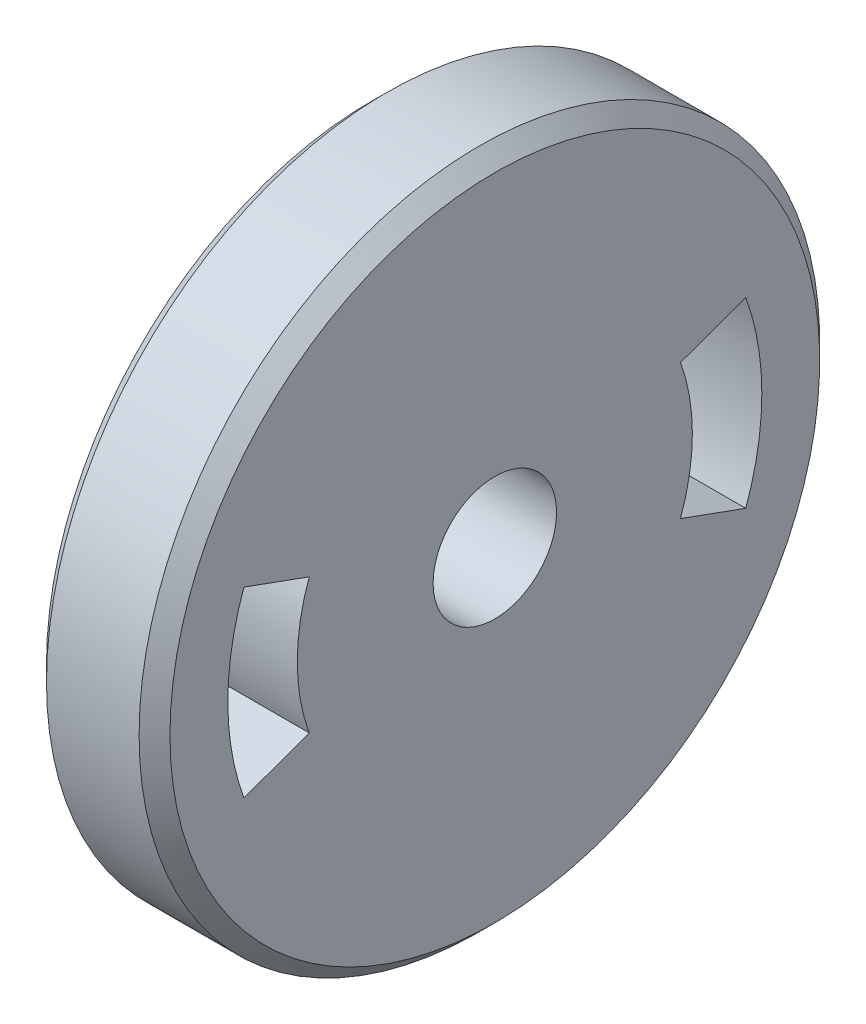
SolidWorks part; units mm, degrees
ref_plane "Front Plane" through (0, 0, 0) normal (0, 0, 1) x (1, 0, 0)
ref_plane "Top Plane" through (0, 0, 0) normal (0, 1, 0) x (1, 0, 0)
ref_plane "Right Plane" through (0, 0, 0) normal (1, 0, 0) x (0, 0, -1)
sketch "Sketch1" plane through (0, 0, 0) normal (-1, 0, 0) x (0, 0, 1)
  circle A0 centre (25, 0) radius 22.15 construction
  circle A1 centre (25, 0) radius 22.05
  dimension "D1" = 0.1
extrude "Boss-Extrude1" add sketch "Sketch1" along normal blind 8
sketch "Sketch2" plane through (-8, 0, 0) normal (-1, 0, 0) x (0, 0, 1)
  circle A0 centre (25, 0) radius 4
  dimension "D1" = 8
extrude "Cut-Extrude1" cut sketch "Sketch2" against normal up to next
sketch "Sketch3" plane through (-8, 0, 0) normal (-1, 0, 0) x (0, 0, 1)
  line L0 (25, 0) -> (47.05, 0) construction
  line L1 (25, 0) -> (2.95, 0) construction
  line L2 (25, 0) -> (45.7202, 7.5415) construction
  line L3 (25, 0) -> (8.7435, -5.9169) construction
  line L4 (8.7435, 5.9169) -> (41.2565, -5.9169) construction
  line L5 (12.9721, -4.3778) -> (8.7435, -5.9169)
  line L6 (12.9721, 4.3778) -> (8.7435, 5.9169)
  line L7 (37.0279, -4.3778) -> (41.2565, -5.9169)
  line L8 (37.0279, 4.3778) -> (41.2565, 5.9169)
  circle A0 centre (40.075, 0) radius 3.05 construction
  circle A1 centre (9.925, 0) radius 3.05 construction
  circle A2 centre (40.075, 0) radius 3.05 construction
  circle A3 centre (9.925, 0) radius 3.05 construction
  arc A4 (12.9721, 4.3778) -> (12.9721, -4.3778) centre (25, 0) ccw
  arc A5 (8.7435, 5.9169) -> (8.7435, -5.9169) centre (25, 0) ccw
  circle A7 centre (25, 0) radius 22.05 construction
  arc A8 (41.2565, -5.9169) -> (41.2565, 5.9169) centre (25, 0) ccw
  arc A9 (37.0279, -4.3778) -> (37.0279, 4.3778) centre (25, 0) ccw
  dimension "D3" = 20
  dimension "D4" = 20
  dimension "D1" = 4.5
extrude "Cut-Extrude2" cut sketch "Sketch3" against normal up to next
fillet "Fillet1" radius 1 2 edges at (0, 0, 47.05) (-8, 0, 47.05) profile chamfer
sketch "Sketch4" plane through (-8, 0, 0) normal (-1, 0, 0) x (0, 0, 1)
  line L0 (25, -111910.8353) -> (25, 111863.5728) construction
  line L1 (19, 2.7) -> (33, 2.7) construction
  line L2 (19, 2.7) -> (19, -5.3) construction
  line L3 (19, -5.3) -> (33, -5.3) construction
  line L4 (33, 2.7) -> (33, -5.3) construction
  line L5 (19, 2.7) -> (33, -5.3) construction
  line L6 (19, -5.3) -> (33, 2.7) construction
  line L8 (32, -11.3) -> (18, -11.3)
  line L9 (32, -11.3) -> (32, 8.7)
  line L10 (32, 8.7) -> (18, 8.7)
  line L11 (18, -11.3) -> (18, 8.7)
  line L12 (32, -11.3) -> (18, 8.7) construction
  line L13 (32, 8.7) -> (18, -11.3) construction
  circle A0 centre (25, 0) radius 4
  point P11 (25, -1.3)
  dimension "D5" = 8
  dimension "D1" = 8
  dimension "D3" = 6
  dimension "D4" = 2.7
  dimension "D6" = 6
  dimension "D7" = 6
  dimension "D8" = 7
  dimension "D2" = 7
extrude "Boss-Extrude2" add sketch "Sketch4" along normal blind 6
sketch "Sketch6" plane through (-14, 0, 0) normal (-1, 0, 0) x (0, 0, 1)
  line L1 (18.95, -5.35) -> (31.05, -5.35)
  line L2 (18.95, -5.35) -> (18.95, 2.75)
  line L3 (18.95, 2.75) -> (31.05, 2.75)
  line L4 (31.05, -5.35) -> (31.05, 2.75)
  line L5 (18.95, -5.35) -> (31.05, 2.75) construction
  line L6 (18.95, 2.75) -> (31.05, -5.35) construction
  line L8 (32, 8.7) -> (18, 8.7) construction
  line L9 (18, -11.3) -> (32, -11.3) construction
  line L11 (32, -11.3) -> (32, 8.7) construction
  point P4 (25, -1.3)
  dimension "D1" = 5.95
  dimension "D2" = 5.95
  dimension "D3" = 12.1
  dimension "D4" = 7
extrude "Cut-Extrude3" cut sketch "Sketch6" against normal blind 2
sketch "Sketch7" plane through (-14, 0, 0) normal (-1, 0, 0) x (0, 0, 1)
  line L0 (25, -111910.8353) -> (25, 111863.5728) construction
  line L1 (32, 8.7) -> (18, 8.7) construction
  line L2 (18, -11.3) -> (32, -11.3) construction
  circle A0 centre (25, 5.95) radius 1.25
  circle A1 centre (25, -8.55) radius 1.25
  dimension "D1" = 2.5
  dimension "D2" = 2.75
  dimension "D3" = 2.75
extrude "Cut-Extrude4" cut sketch "Sketch7" against normal blind 8
fillet "Fillet2" radius 1 4 edges at (-8, -11.3, 25) (-8, -1.3, 32) (-8, 8.7, 25) (-8, -1.3, 18)
equation "\"D4@Sketch3\"=\"D3@Sketch3\""
equation "\"D7@Sketch4\"=\"D6@Sketch4\""
equation "\"D3@Sketch7\"=\"D2@Sketch7\""
